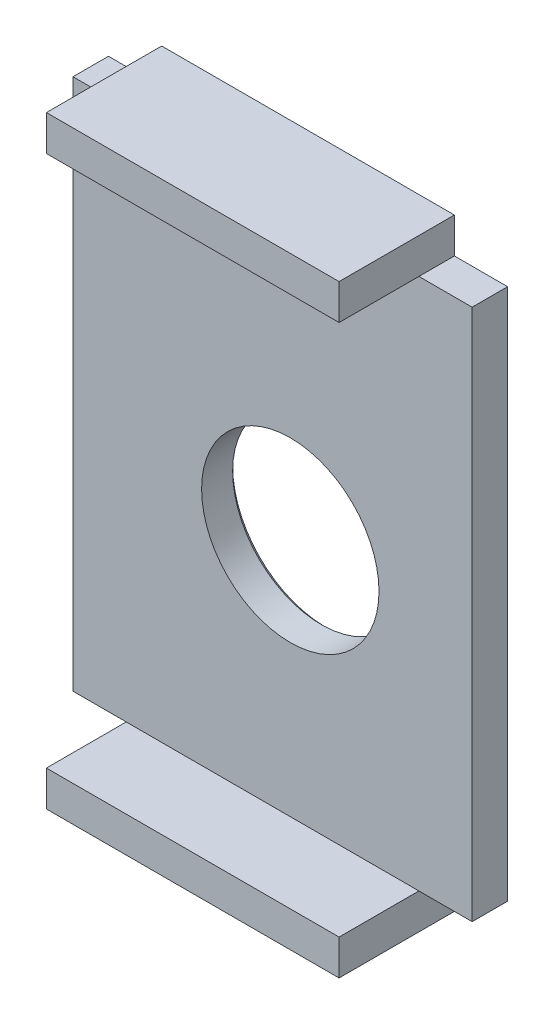
SolidWorks part; units mm, degrees
ref_plane "Front Plane" through (0, 0, 0) normal (0, 0, 1) x (1, 0, 0)
ref_plane "Top Plane" through (0, 0, 0) normal (0, 1, 0) x (1, 0, 0)
ref_plane "Right Plane" through (0, 0, 0) normal (1, 0, 0) x (0, 0, -1)
sketch "Sketch1" plane through (0, 0, 0) normal (0, 0, 1) x (1, 0, 0)
  line L5 (-22.5, -30) -> (22.5, -30)
  line L6 (-22.5, -30) -> (-22.5, 30)
  line L7 (-22.5, 30) -> (22.5, 30)
  line L8 (22.5, -30) -> (22.5, 30)
  line L9 (-22.5, -30) -> (22.5, 30) construction
  line L10 (-22.5, 30) -> (22.5, -30) construction
  circle A2 centre (2, -3) radius 10
  point P0 (0, 0)
  dimension "D3" = 20
  dimension "D1" = 60
  dimension "D2" = 45
  dimension "D4" = 20.5
  dimension "D5" = 3
extrude "Boss-Extrude1" add sketch "Sketch1" along normal mid plane 4
sketch "Sketch3" plane through (0, 0, -2) normal (0, 0, -1) x (-1, 0, 0)
  line L0 (-22.5, 30) -> (22.5, 30) construction
  line L1 (-16.5, 30) -> (16.5, 30)
  line L2 (-16.5, 30) -> (-16.5, 34)
  line L3 (-16.5, 34) -> (16.5, 34)
  line L4 (16.5, 30) -> (16.5, 34)
  line L5 (-22.5, -30) -> (-22.5, 30) construction
  line L6 (22.5, 30) -> (22.5, -30) construction
  line L7 (22.5, -30) -> (-22.5, -30) construction
  line L8 (-16.5, -30) -> (16.5, -30)
  line L9 (-16.5, -30) -> (-16.5, -34)
  line L10 (-16.5, -34) -> (16.5, -34)
  line L11 (16.5, -30) -> (16.5, -34)
  dimension "D1" = 6
  dimension "D2" = 6
  dimension "D3" = 4
extrude "Boss-Extrude3" add sketch "Sketch3" against normal blind 13
chamfer "Chamfer1" distance 0.5 angle 45 1 edges at (12, -3, -2)
equation "\"padding\"=6"
equation "\"wall_thick_ness\"=4"
equation "\"D1@Sketch3\"=\"padding\""
equation "\"D2@Sketch3\"=\"padding\""
equation "\"D3@Sketch3\"=\"wall_thick_ness\""
equation "\"D1@Boss-Extrude1\"=\"wall_thick_ness\""
